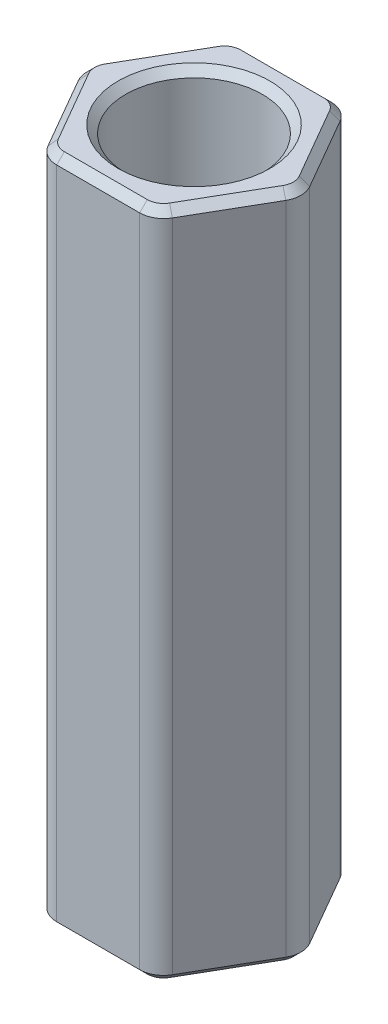
SolidWorks part; units mm, degrees
ref_plane "Front Plane" through (0, 0, 0) normal (0, 0, 1) x (1, 0, 0)
ref_plane "Top Plane" through (0, 0, 0) normal (0, 1, 0) x (1, 0, 0)
ref_plane "Right Plane" through (0, 0, 0) normal (1, 0, 0) x (0, 0, -1)
sketch "Sketch1" plane through (0, 0, 0) normal (0, 1, 0) x (1, 0, 0)
  line L1 (0.9165, 1.5875) -> (-0.9165, 1.5875)
  line L2 (-0.9165, 1.5875) -> (-1.8331, 0)
  line L3 (-1.8331, 0) -> (-0.9165, -1.5875)
  line L4 (-0.9165, -1.5875) -> (0.9165, -1.5875)
  line L5 (0.9165, -1.5875) -> (1.8331, 0)
  line L6 (1.8331, 0) -> (0.9165, 1.5875)
  circle A0 centre (0, 0) radius 1.5875 construction
  dimension "D1" = 3.175
extrude "Boss-Extrude1" add sketch "Sketch1" along normal mid plane 11.1125 contours L1 L2 L3 L4 L5 L6
hole_wizard "#4-40 Tapped Hole1" positions "Sketch2" profile "Sketch3" tap size "#4-40" standard "ANSI Inch" end condition through all
sketch "Sketch2" plane through (0, 5.5562, 0) normal (0, 1, 0) x (1, 0, 0)
  point P0 (0, 0)
sketch "Sketch3" plane through (0, 5.5562, 0) normal (1, 0, 0) x (0, 0, 1)
  line L0 (0, 0) -> (0, 11.1125)
  line L1 (0, 11.1125) -> (1.1303, 11.1125)
  line L2 (1.1303, 11.1125) -> (1.1303, 0)
  line L5 (1.1303, 0) -> (0, 0)
  line L11 (0, -6.35) -> (0, 107.95) construction
  dimension "Thru Tap Drill Dia." = 2.2606
  dimension "Thru Tap Drill Depth" = 11.1125
cosmetic thread "Hole Thread1" parameters "D2"=2.8448
fillet "Fillet1" radius 0.3969 6 edges at (-0.9165, 0, -1.5875) (0.9165, 0, -1.5875) (1.8331, 0, 0) (0.9165, 0, 1.5875) (-0.9165, 0, 1.5875) (-1.8331, 0, 0)
chamfer "Chamfer1" distance 0.127 angle 45 26 edges at (0, 5.5563, 1.1303) (0, -5.5562, 1.1303) (1.3748, -5.5562, -0.7938) (0.8858, -5.5562, -1.5343) (1.7717, -5.5562, 0) (0, -5.5562, -1.5875) (1.3748, -5.5562, 0.7937) (-0.8858, -5.5562, -1.5343) (0.8858, -5.5562, 1.5343) (-1.3748, -5.5562, -0.7937) (0, -5.5562, 1.5875) (-1.7717, -5.5562, 0) (-0.8858, -5.5562, 1.5343) (-1.3748, -5.5562, 0.7938) (1.3748, 5.5562, -0.7938) (0.8858, 5.5562, -1.5343) (1.7717, 5.5562, 0) (0, 5.5562, -1.5875) (1.3748, 5.5562, 0.7937) (-0.8858, 5.5562, -1.5343) (0.8858, 5.5562, 1.5343) (-1.3748, 5.5562, -0.7937) (0, 5.5562, 1.5875) (-1.7717, 5.5562, 0) (-0.8858, 5.5562, 1.5343) (-1.3748, 5.5562, 0.7938)
